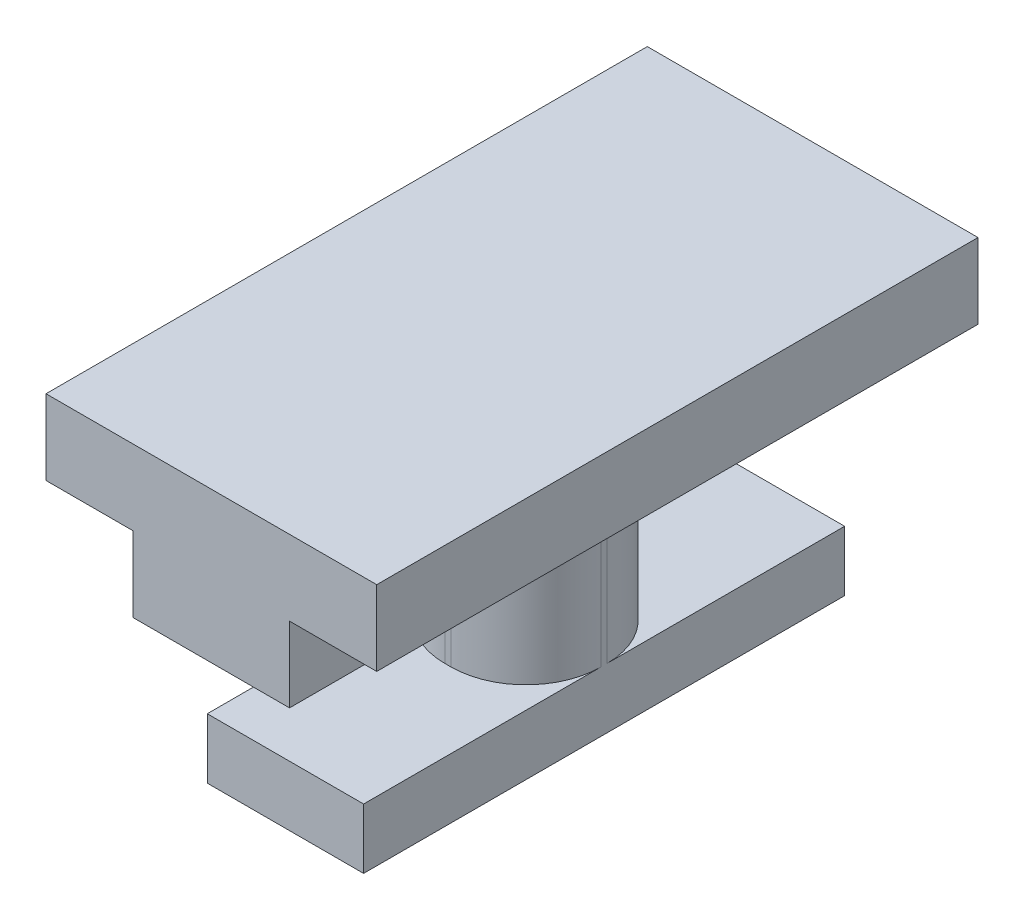
SolidWorks part; units mm, degrees
ref_plane "Alzado" through (0, 0, 0) normal (0, 0, 1) x (1, 0, 0)
ref_plane "Planta" through (0, 0, 0) normal (0, 1, 0) x (1, 0, 0)
ref_plane "Vista lateral" through (0, 0, 0) normal (1, 0, 0) x (0, 0, -1)
sketch "Croquis1" plane through (0, 0, 0) normal (0, 0, 1) x (1, 0, 0)
  line L0 (-5.5, 0) -> (5.5, 0)
  line L1 (5.5, 0) -> (5.5, -2.5)
  line L2 (5.5, -2.5) -> (2.6, -2.5)
  line L3 (2.6, -2.5) -> (2.6, -5)
  line L4 (2.6, -5) -> (-2.6, -5)
  line L5 (0, 0) -> (0, -5) construction
  line L6 (-2.6, -2.5) -> (-2.6, -5)
  line L7 (-5.5, -2.5) -> (-2.6, -2.5)
  line L8 (-5.5, 0) -> (-5.5, -2.5)
  dimension "D1" = 5.5
  dimension "D2" = 2.5
  dimension "D3" = 2.5
  dimension "D4" = 2.9
extrude "Saliente-Extruir1" add sketch "Croquis1" along normal blind 20
sketch "Croquis2" plane through (0, -5, 0) normal (0, -1, 0) x (1, 0, 0)
  line L2 (-2.6, 6.9359) -> (2.6, 6.9359)
  line L3 (-2.6, 6.9359) -> (-2.6, 12.1359)
  line L4 (2.6, 6.9359) -> (2.6, 12.1359)
  line L5 (-2.6, 12.1359) -> (2.6, 12.1359)
  line L6 (-2.6, 6.9359) -> (2.6, 12.1359) construction
  line L7 (2.6, 6.9359) -> (-2.6, 12.1359) construction
  dimension "D1" = 5.2
  dimension "D2" = 5.2
extrude "Saliente-Extruir2" add sketch "Croquis2" along normal blind 4
sketch "Croquis3" plane through (0, -9, 0) normal (0, -1, 0) x (1, 0, 0)
  line L0 (2.6, 17.5359) -> (-2.6, 17.5359)
  line L1 (2.6, 6.9359) -> (2.6, 0) construction
  line L2 (-2.6, 20) -> (-2.6, 12.1359) construction
  line L3 (2.6, 20) -> (2.6, 0) construction
  line L4 (2.6, 1.5359) -> (2.6, 17.5359)
  line L5 (-2.6, 17.5359) -> (-2.6, 1.5359)
  line L6 (-2.6, 20) -> (-2.6, 0) construction
  line L7 (-2.6, 1.5359) -> (2.6, 1.5359)
  dimension "D1" = 16
extrude "Saliente-Extruir4" add sketch "Croquis3" along normal blind 2
fillet "Redondeo4" radius 2.5 4 edges at (-2.6, -7, 12.1359) (-2.6, -7, 6.9359) (2.6, -7, 12.1359) (2.6, -7, 6.9359)
